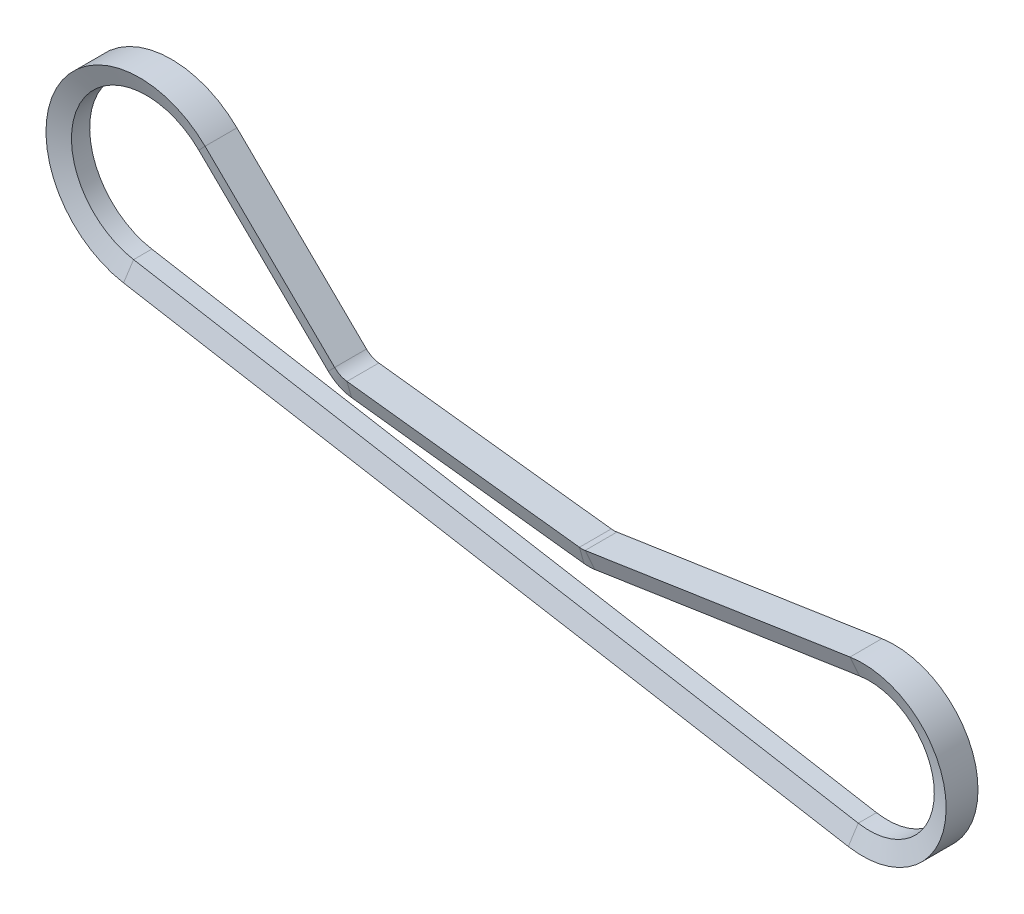
SolidWorks part; units mm, degrees
ref_plane "Front Plane" through (0, 0, 0) normal (0, 0, 1) x (1, 0, 0)
ref_plane "Top Plane" through (0, 0, 0) normal (0, 1, 0) x (1, 0, 0)
ref_plane "Right Plane" through (0, 0, 0) normal (1, 0, 0) x (0, 0, -1)
sketch "Sketch2" plane through (0, 0, 0) normal (0, 0, 1) x (1, 0, 0)
  line L0 (0, 0) -> (1, 0) construction
  line L1 (0, 0) -> (0, 1) construction
  line L12 (-4.2729, -24.6321) -> (-221.0156, 12.966)
  line L14 (-196.6457, 60.5654) -> (-157.8991, 22.646)
  line L15 (-154.2024, 20.8782) -> (-84.6854, 12.6689)
  line L16 (-82.9884, 12.6969) -> (-3.7495, 24.7172)
  arc A4 (-221.0156, 12.966) -> (-196.6457, 60.5654) centre (-216.2299, 40.554) cw
  arc A7 (-3.7495, 24.7172) -> (-4.2729, -24.6321) centre (0, 0) cw
  arc A8 (-157.8991, 22.646) -> (-154.2024, 20.8782) centre (-153.4577, 27.1843) ccw
  arc A9 (-84.6854, 12.6689) -> (-82.9884, 12.6969) centre (-83.9407, 18.9751) ccw
ref_plane "Plane4" through (-3.7495, 24.7172, 0) normal (0.9887, 0.15, 0) x (0.15, -0.9887, 0)
sketch "Sketch3" plane through (-3.7495, 24.7172, 0) normal (0.9887, 0.15, 0) x (0.15, -0.9887, 0)
  line L0 (0, -4.7625) -> (0, 4.7625)
  line L1 (0, -4.7625) -> (5.588, -2.7286)
  line L2 (5.588, -2.7286) -> (5.588, 2.7286)
  line L3 (5.588, 2.7286) -> (0, 4.7625)
  line L4 (0, 0) -> (5.588, 0) construction
  dimension "D1" = 9.525
  dimension "D2" = 5.588
  dimension "D3" = 40
sweep "Sweep1" add profiles "Sketch3" path "Sketch2"
